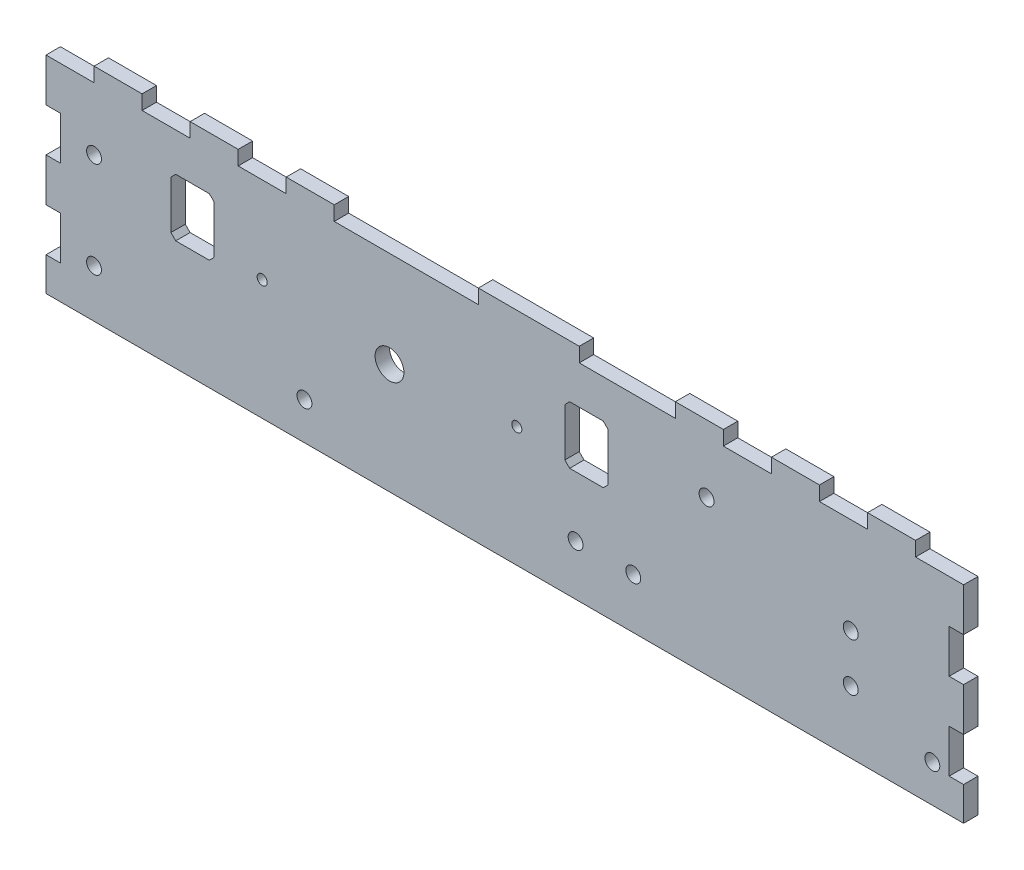
SolidWorks part; units mm, degrees
ref_plane "Front Plane" through (0, 0, 0) normal (0, 0, 1) x (1, 0, 0)
ref_plane "Top Plane" through (0, 0, 0) normal (0, 1, 0) x (1, 0, 0)
ref_plane "Right Plane" through (0, 0, 0) normal (1, 0, 0) x (0, 0, -1)
sketch "Sketch1" plane through (0, 0, 0) normal (0, 0, 1) x (1, 0, 0)
  line L4 (-191, 0) -> (0, 0)
  line L5 (0, 0) -> (0, 46)
  line L6 (0, 46) -> (-191, 46)
  line L7 (-191, 46) -> (-191, 0)
  line L8 (-191, 0) -> (0, 0)
  line L9 (0, 0) -> (0, 46)
  line L10 (0, 46) -> (-191, 46)
  line L11 (-191, 46) -> (-191, 0)
  circle A0 centre (-181, 30) radius 1.55 construction
  circle A1 centre (-181, 10) radius 1.55 construction
  circle A2 centre (-181, 30) radius 1.55
  circle A3 centre (-181, 10) radius 1.55
  dimension "D1" = 0
extrude "Boss-Extrude1" add sketch "Sketch1" along normal blind 3
sketch "Sketch5" plane through (0, 0, 3) normal (0, 0, 1) x (1, 0, 0)
  line L0 (-95.5, 0) -> (-95.5, 46) construction
  line L1 (-191, 0) -> (0, 0) construction
  line L2 (0, 46) -> (-191, 46) construction
ref_axis "Axis1" through (-95.5, 0, 3) along (0, 1, 0)
ref_plane "Plane1" through (-95.5, 0, 0) normal (1, 0, 0) x (0, 1, 0)
sketch "Sketch2" plane through (0, 0, 3) normal (0, 0, 1) x (1, 0, 0)
  line L0 (-119.5, 46) -> (-119.5, 0) construction
  line L1 (-119.5, 46) -> (-119.5, 0)
  point P2 (-119.5, 23)
ref_point "MointPoint-Sus"
sketch "Sketch3" plane through (0, 0, 0) normal (0, 0, -1) x (-1, 0, 0)
  line L4 (50, 43) -> (50, 46)
  line L5 (50, 46) -> (40, 46)
  line L6 (40, 46) -> (40, 43)
  line L7 (40, 43) -> (50, 43)
  line L8 (50, 43) -> (50, 46)
  line L9 (50, 46) -> (40, 46)
  line L10 (40, 46) -> (40, 43)
  line L11 (40, 43) -> (50, 43)
  line L12 (30, 43) -> (30, 46)
  line L13 (30, 46) -> (20, 46)
  line L14 (20, 46) -> (20, 43)
  line L15 (20, 43) -> (30, 43)
  line L16 (30, 43) -> (30, 46)
  line L17 (30, 46) -> (20, 46)
  line L18 (20, 46) -> (20, 43)
  line L19 (20, 43) -> (30, 43)
  line L20 (10, 43) -> (10, 46)
  line L21 (10, 46) -> (0, 46)
  line L22 (0, 46) -> (0, 43)
  line L23 (0, 43) -> (10, 43)
  line L24 (10, 43) -> (10, 46)
  line L25 (10, 46) -> (0, 46)
  line L26 (0, 46) -> (0, 43)
  line L27 (0, 43) -> (10, 43)
  line L28 (171, 43) -> (171, 46)
  line L29 (171, 46) -> (161, 46)
  line L30 (161, 46) -> (161, 43)
  line L31 (161, 43) -> (171, 43)
  line L32 (171, 43) -> (171, 46)
  line L33 (171, 46) -> (161, 46)
  line L34 (161, 46) -> (161, 43)
  line L35 (161, 43) -> (171, 43)
  line L36 (151, 43) -> (151, 46)
  line L37 (151, 46) -> (141, 46)
  line L38 (141, 46) -> (141, 43)
  line L39 (141, 43) -> (151, 43)
  line L40 (151, 43) -> (151, 46)
  line L41 (151, 46) -> (141, 46)
  line L42 (141, 46) -> (141, 43)
  line L43 (141, 43) -> (151, 43)
  line L44 (131, 46) -> (101, 46)
  line L45 (101, 46) -> (101, 43)
  line L46 (101, 43) -> (131, 43)
  line L47 (131, 43) -> (131, 46)
  line L48 (131, 46) -> (101, 46)
  line L49 (101, 46) -> (101, 43)
  line L50 (101, 43) -> (131, 43)
  line L51 (131, 43) -> (131, 46)
  line L52 (80, 46) -> (60, 46)
  line L53 (80, 43) -> (80, 46)
  line L54 (60, 43) -> (80, 43)
  line L55 (60, 46) -> (60, 43)
  line L56 (80, 46) -> (60, 46)
  line L57 (80, 43) -> (80, 46)
  line L58 (60, 43) -> (80, 43)
  line L59 (60, 46) -> (60, 43)
  line L60 (181, 43) -> (191, 43)
  line L61 (181, 46) -> (181, 43)
  line L62 (191, 46) -> (181, 46)
  line L63 (191, 43) -> (191, 46)
  line L64 (181, 43) -> (191, 43)
  line L65 (181, 46) -> (181, 43)
  line L66 (191, 46) -> (181, 46)
  line L67 (191, 43) -> (191, 46)
  dimension "D1" = 0
  dimension "D2" = 0
  dimension "D3" = 0
  dimension "D4" = 0
  dimension "D5" = 0
  dimension "D6" = 0
  dimension "D7" = 0
  dimension "D8" = 0
extrude "Cut-Extrude1" cut sketch "Sketch3" against normal up to next
sketch "Sketch4" plane through (0, 0, 3) normal (0, 0, 1) x (1, 0, 0)
  line L0 (-3, 43) -> (-3, 0) construction
  line L1 (0, 43) -> (-10, 43) construction
  line L2 (-191, 0) -> (0, 0) construction
  line L3 (0, 0) -> (0, 43) construction
  line L4 (-3, 34) -> (0, 34)
  line L5 (-3, 25) -> (0, 25)
  line L6 (-3, 16) -> (0, 16)
  line L7 (-3, 7) -> (0, 7)
  line L8 (0, 34) -> (0, 25)
  line L9 (-3, 25) -> (-3, 34)
  line L10 (0, 16) -> (0, 7)
  line L11 (-3, 7) -> (-3, 16)
  dimension "D1" = 3
  dimension "D2" = 9
  dimension "D3" = 4
extrude "Cut-Extrude2" cut sketch "Sketch4" against normal up to next
mirror "Mirror1" about plane through (-95.5, 0, 0) normal (1, 0, 0) of "Cut-Extrude2"
sketch "Sketch6" plane through (0, 0, 3) normal (0, 0, 1) x (1, 0, 0)
  circle A0 centre (-119.5, 23) radius 3
  point P0 (-119.5, 23)
  dimension "D1" = 6
extrude "Cut-Extrude3" cut sketch "Sketch6" against normal up to next
sketch "Sketch7" plane through (0, 0, 3) normal (0, 0, 1) x (1, 0, 0)
  circle A0 centre (-53.5, 32) radius 1.55 construction
  circle A1 centre (-68.7574, 10.5) radius 1.55 construction
  circle A2 centre (-80.7574, 10.5) radius 1.55 construction
  circle A3 centre (-23.5, 23) radius 1.55 construction
  circle A4 centre (-23.5, 13) radius 1.55 construction
  circle A5 centre (-53.5, 32) radius 1.55
  circle A6 centre (-68.7574, 10.5) radius 1.55
  circle A7 centre (-80.7574, 10.5) radius 1.55
  circle A8 centre (-23.5, 23) radius 1.55
  circle A9 centre (-23.5, 13) radius 1.55
extrude "Cut-Extrude4" cut sketch "Sketch7" against normal up to next
sketch "Sketch8" plane through (0, 0, 0) normal (0, 0, -1) x (-1, 0, 0)
  circle A0 centre (137.2, 7.8) radius 1.55 construction
  circle A1 centre (6.5, 7.8) radius 1.55 construction
  circle A2 centre (137.2, 7.8) radius 1.55
  circle A3 centre (6.5, 7.8) radius 1.55
extrude "Cut-Extrude5" cut sketch "Sketch8" against normal up to next
sketch "Sketch9" plane through (0, 0, 3) normal (0, 0, 1) x (1, 0, 0)
  line L0 (-84.7574, 18) -> (-69, 18) construction
  line L1 (-83, 35) -> (-74, 35)
  line L2 (-83, 35) -> (-83, 23)
  line L3 (-83, 23) -> (-74, 23)
  line L4 (-74, 35) -> (-74, 23)
  circle A0 centre (-93, 25) radius 1.05
  dimension "D5" = 2.1
  dimension "D1" = 12
  dimension "D2" = 9
  dimension "D3" = 8
  dimension "D4" = 5
  dimension "D6" = 10
  dimension "D7" = 2
extrude "Cut-Extrude6" cut sketch "Sketch9" against normal up to next
chamfer "Chamfer1" distance 1 angle 45 4 edges at (-83, 35, 1.5) (-83, 23, 1.5) (-74, 23, 1.5) (-74, 35, 1.5)
sketch "Sketch10" plane through (0, 0, 3) normal (0, 0, 1) x (1, 0, 0)
  line L0 (-119.5, 23) -> (-119.5, 38.3584) construction
  line L1 (-82, 23) -> (-75, 23) construction
  line L2 (-82, 23) -> (-83, 24) construction
  line L3 (-83, 34) -> (-83, 24) construction
  line L4 (-83, 34) -> (-82, 35) construction
  line L5 (-75, 35) -> (-82, 35) construction
  line L6 (-75, 35) -> (-74, 34) construction
  line L7 (-74, 24) -> (-74, 34) construction
  line L8 (-74, 24) -> (-75, 23) construction
  line L9 (-82, 23) -> (-75, 23)
  line L10 (-82, 23) -> (-83, 24)
  line L11 (-83, 34) -> (-83, 24)
  line L12 (-83, 34) -> (-82, 35)
  line L13 (-75, 35) -> (-82, 35)
  line L14 (-75, 35) -> (-74, 34)
  line L15 (-74, 24) -> (-74, 34)
  line L16 (-74, 24) -> (-75, 23)
  line L17 (-165, 24) -> (-164, 23)
  line L18 (-165, 24) -> (-165, 34)
  line L19 (-164, 35) -> (-165, 34)
  line L20 (-164, 35) -> (-157, 35)
  line L21 (-156, 34) -> (-157, 35)
  line L22 (-156, 34) -> (-156, 24)
  line L23 (-157, 23) -> (-156, 24)
  line L24 (-157, 23) -> (-164, 23)
  circle A0 centre (-93, 25) radius 1.05 construction
  circle A1 centre (-93, 25) radius 1.05
  circle A2 centre (-146, 25) radius 1.05
extrude "Cut-Extrude7" cut sketch "Sketch10" against normal up to next contours L24 L23 L22 L21 L20 L19 L18 L17 | A2 region at (-160.5, 29, 3) region at (-146, 25, 3)
